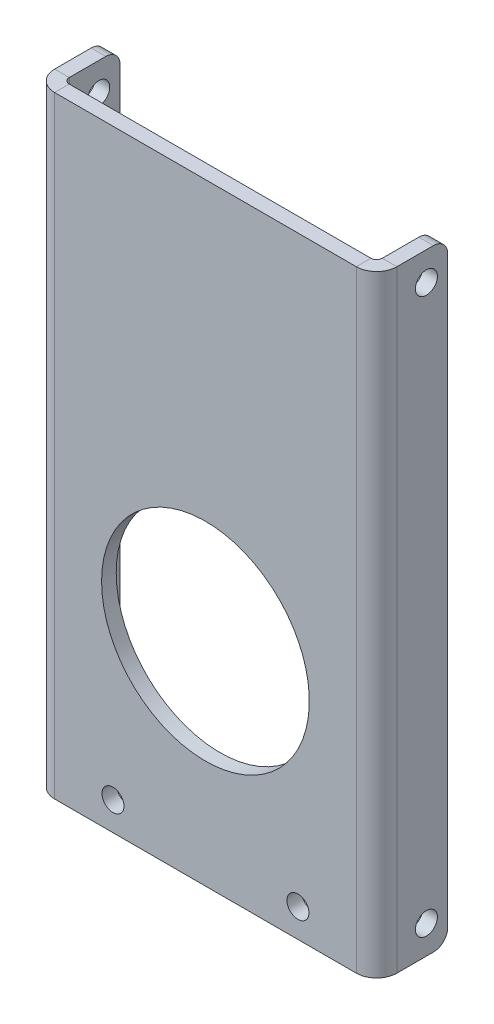
SolidWorks part; units mm, degrees
note: The reader was unsure of these and kept them because the rebuilt part matched: flange length of "Edge-Flange1".
material "5052-H32"
ref_plane "Front Plane" through (0, 0, 0) normal (0, 0, 1) x (1, 0, 0)
ref_plane "Top Plane" through (0, 0, 0) normal (0, 1, 0) x (1, 0, 0)
ref_plane "Right Plane" through (0, 0, 0) normal (1, 0, 0) x (0, 0, -1)
sketch "Sketch1" plane through (0, 0, 0) normal (0, 0, 1) x (1, 0, 0)
  line L0 (-38.1889, 0) -> (38.1889, 0) construction
  line L1 (-38.1889, 89.1964) -> (38.1889, 89.1964)
  line L2 (-38.1889, 89.1964) -> (-38.1889, -47.3286)
  line L3 (-38.1889, -47.3286) -> (38.1889, -47.3286)
  line L4 (38.1889, 89.1964) -> (38.1889, -47.3286)
  point P6 (0, 0)
  dimension "D1" = 47.3286
  dimension "D2" = 76.3778
  dimension "D3" = 136.525
base flange "Base-Flange1" sketch "Sketch1" thickness 3.2639 reverse thickness direction no parameters "D1"=1.27
edge flange "Edge-Flange1" sketch "Sketch27" flange profiles "Sketch27", "Sketch28" flange angle 90 flange length 15.875 flange position material inside bend radius 1.27 thickness 3.2639 relief rectangular parameters "D6"=10, "D8"=0.254
sketch "Sketch27" plane through (38.1889, 0, -3.2639) normal (-1, 0, 0) x (0, 1, 0)
  line L2 (-47.3286, 0) -> (-47.3286, 12.6111)
  line L3 (-47.3286, 12.6111) -> (89.1964, 12.6111)
  line L4 (89.1964, 12.6111) -> (89.1964, 0)
  line L5 (89.1964, 0) -> (-47.3286, 0) construction
  line L6 (89.1964, 0) -> (-47.3286, 0)
sketch "Sketch28" plane through (-38.1889, 0, -3.2639) normal (1, 0, 0) x (0, -1, 0)
  line L0 (47.3286, 0) -> (-89.1964, 0) construction
  line L1 (47.3286, 0) -> (-89.1964, 0)
  line L2 (47.3286, 0) -> (47.3286, 12.6111)
  line L3 (47.3286, 12.6111) -> (-89.1964, 12.6111)
  line L4 (-89.1964, 12.6111) -> (-89.1964, 0)
bend "EdgeBend1" bend radius 1.27 bend angle 90 parameters "D5"=1
bend "EdgeBend2" bend radius 1.27 bend angle 90 parameters "D5"=2
sketch "Sketch29" plane through (38.1889, 0, 0) normal (1, 0, 0) x (0, 0, -1)
  line L0 (11.1125, 82.8464) -> (11.1125, -40.9786) construction
  line L1 (15.875, -47.3286) -> (4.5339, -47.3286) construction
  line L2 (4.5339, 89.1964) -> (15.875, 89.1964) construction
  line L3 (0, -47.3286) -> (0, 89.1964) construction
  dimension "D1" = 6.35
  dimension "D2" = 6.35
  dimension "D3" = 11.1125
hole_wizard "#10 (0.1935) Diameter Hole1" positions "Sketch30" profile "Sketch31" hole size "#10" standard "ANSI Inch" end condition through all
sketch "Sketch30" plane through (38.1889, 0, 0) normal (1, 0, 0) x (0, 0, -1)
  point P0 (11.1125, 82.8464)
  point P3 (11.1125, -40.9786)
sketch "Sketch31" plane through (38.1889, 82.8464, -11.1125) normal (0, 1, 0) x (0, 0, -1)
  line L0 (0, 0) -> (0, 76.3778)
  line L1 (0, 76.3778) -> (2.4574, 76.3778)
  line L2 (2.4574, 76.3778) -> (2.4574, 0)
  line L5 (2.4574, 0) -> (0, 0)
  line L11 (0, -6.35) -> (0, 107.95) construction
  dimension "Thru Hole Dia." = 4.9149
  dimension "Thru Hole Depth" = 76.3778
sketch "Sketch32" plane through (0, 0, -3.2639) normal (0, 0, -1) x (-1, 0, 0)
  circle A0 centre (0, 0) radius 23.1775
  dimension "D1" = 46.355
extrude "Cut-Extrude1" cut sketch "Sketch32" against normal through all normal cut yes
sketch "Sketch33" plane through (0, 0, 0) normal (0, 0, 1) x (1, 0, 0)
  line L0 (-20.6375, -40.9786) -> (20.6375, -40.9786) construction
  line L1 (-38.1889, -47.3286) -> (38.1889, -47.3286) construction
  point P2 (0, -40.9786)
  dimension "D1" = 6.35
  dimension "D2" = 41.275
hole_wizard "#10 (0.1935) Diameter Hole2" positions "Sketch34" profile "Sketch35" hole size "#10" standard "ANSI Inch" end condition up to next
sketch "Sketch34" plane through (0, 0, 0) normal (0, 0, 1) x (1, 0, 0)
  point P0 (-20.6375, -40.9786)
  point P3 (20.6375, -40.9786)
sketch "Sketch35" plane through (-20.6375, -40.9786, 0) normal (1, 0, 0) x (0, -1, 0)
  line L0 (0, 0) -> (0, 3.2639)
  line L1 (0, 3.2639) -> (2.4574, 3.2639)
  line L2 (2.4574, 3.2639) -> (2.4574, 0)
  line L5 (2.4574, 0) -> (0, 0)
  line L11 (0, -6.35) -> (0, 107.95) construction
  dimension "Thru Hole Dia." = 4.9149
  dimension "Thru Hole Depth" = 3.2639
fillet "Fillet1" radius 3.175 4 edges at (-36.557, 89.1964, -15.875) (36.557, 89.1964, -15.875) (-36.557, -47.3286, -15.875) (36.557, -47.3286, -15.875)
sketch "Bend-Lines1" [suppressed] plane through (0, 0, 0) normal (0, 1, 0) x (1, 0, 0)
sketch "Bounding-Box1" [suppressed] plane through (0, 0, 0) normal (0, 1, 0) x (1, 0, 0)
sheet metal parameters "Sheet-Metal1" thickness 3.2639 parameters "D1"=1.27
flat pattern "Flat-Pattern1" [suppressed]
sketch "Bend-Lines2" plane through (0, 0, 0) normal (0, 1, 0) x (1, 0, 0)
sketch3d "Bounding-Box2" [suppressed]
  line L0 (38.1, 56.2696, 0) -> (38.1, -45.3304, 0) construction
  line L1 (-38.1, 56.2696, 0) -> (-38.1, -45.3304, 0) construction
  line L2 (38.1, 56.2696, 0) -> (-38.1, 56.2696, 0) construction
  line L3 (38.1, -45.3304, 0) -> (-38.1, -45.3304, 0) construction
sheet metal parameters "Sheet-Metal8" thickness 3.2639 parameters "D1"=1.27
flat pattern "Flat-Pattern1"
sketch "Bend-Lines2" plane through (0, 0, 0) normal (0, 0, 1) x (1, 0, 0)
  line L0 (-35.8453, 56.2696) -> (-35.8453, -45.3304) construction
  line L1 (35.8453, -45.3304) -> (35.8453, 56.2696) construction
  line L2 (-35.8453, 56.2696) -> (-35.8453, -45.3304) construction
  line L3 (35.8453, -45.3304) -> (35.8453, 56.2696) construction
sketch3d "Bounding-Box2" [suppressed]
  line L0 (49.4656, 56.2696, 0) -> (49.4656, -45.3304, 0) construction
  line L1 (-49.4656, 56.2696, 0) -> (-49.4656, -45.3304, 0) construction
  line L2 (49.4656, 56.2696, 0) -> (-49.4656, 56.2696, 0) construction
  line L3 (49.4656, -45.3304, 0) -> (-49.4656, -45.3304, 0) construction
bend of the flat pattern "Flatten-<EdgeBend1>1"
bend of the flat pattern "Flatten-<EdgeBend2>1"
sheet metal parameters "Sheet-Metal9" thickness 3.2639 parameters "D1"=1.27
flat pattern "Flat-Pattern1" [suppressed]
sketch "Bend-Lines2" plane through (0, 0, 0) normal (0, 0, 1) x (1, 0, 0)
  line L0 (-35.8453, 56.2696) -> (-35.8453, -45.3304) construction
  line L1 (35.8453, -45.3304) -> (35.8453, 56.2696) construction
  line L2 (-35.8453, 56.2696) -> (-35.8453, -45.3304) construction
  line L3 (35.8453, -45.3304) -> (35.8453, 56.2696) construction
sketch3d "Bounding-Box2" [suppressed]
  line L0 (49.4656, 56.2696, 0) -> (49.4656, -45.3304, 0) construction
  line L1 (-49.4656, 56.2696, 0) -> (-49.4656, -45.3304, 0) construction
  line L2 (49.4656, 56.2696, 0) -> (-49.4656, 56.2696, 0) construction
  line L3 (49.4656, -45.3304, 0) -> (-49.4656, -45.3304, 0) construction
bend of the flat pattern "Flatten-<EdgeBend1>1"
bend of the flat pattern "Flatten-<EdgeBend2>1"
sketch "Sketch29-1" [suppressed] plane through (33.5906, 0, 0) normal (0, 0, 1) x (1, 0, 0)
  line L0 (11.1125, 49.9196) -> (11.1125, -38.9804) construction
  line L1 (15.875, -45.3304) -> (-83.0561, -45.3304)
  line L2 (-83.0561, 56.2696) -> (15.875, 56.2696)
  line L3 (0, -45.3304) -> (0, 56.2696)
  dimension "D1" = 6.35
  dimension "D2" = 6.35
  dimension "D3" = 11.1125
sheet metal parameters "Sheet-Metal10" thickness 3.2639 parameters "D1"=1.27
flat pattern "Flat-Pattern1" [suppressed]
sketch "Bend-Lines2" plane through (0, 0, 0) normal (0, 0, 1) x (1, 0, 0)
  line L0 (-35.8453, 82.8464) -> (-35.8453, -47.3286) construction
  line L1 (35.8453, -47.3286) -> (35.8453, 82.8464) construction
  line L2 (-35.8453, 82.8464) -> (-35.8453, -47.3286) construction
  line L3 (35.8453, -47.3286) -> (35.8453, 82.8464) construction
sketch3d "Bounding-Box2" [suppressed]
  line L0 (49.4656, 82.8464, 0) -> (49.4656, -47.3286, 0) construction
  line L1 (-49.4656, 82.8464, 0) -> (-49.4656, -47.3286, 0) construction
  line L2 (49.4656, 82.8464, 0) -> (-49.4656, 82.8464, 0) construction
  line L3 (49.4656, -47.3286, 0) -> (-49.4656, -47.3286, 0) construction
bend of the flat pattern "Flatten-<EdgeBend1>1"
bend of the flat pattern "Flatten-<EdgeBend2>1"
sketch "Sketch29-1" [suppressed] plane through (33.5906, 0, 0) normal (0, 0, 1) x (1, 0, 0)
  line L0 (11.1125, 76.4964) -> (11.1125, -40.9786) construction
  line L1 (15.875, -47.3286) -> (-83.0561, -47.3286)
  line L2 (-83.0561, 82.8464) -> (15.875, 82.8464)
  line L3 (0, -47.3286) -> (0, 82.8464)
  dimension "D1" = 6.35
  dimension "D2" = 6.35
  dimension "D3" = 11.1125
sheet metal parameters "Sheet-Metal11" thickness 3.2639 parameters "D1"=1.27
flat pattern "Flat-Pattern1" [suppressed]
sketch "Bend-Lines2" plane through (0, 0, 0) normal (0, 0, 1) x (1, 0, 0)
  line L0 (-35.9342, 89.1964) -> (-35.9342, -47.3286) construction
  line L1 (35.9342, -47.3286) -> (35.9342, 89.1964) construction
  line L2 (-35.9342, 89.1964) -> (-35.9342, -47.3286) construction
  line L3 (35.9342, -47.3286) -> (35.9342, 89.1964) construction
sketch3d "Bounding-Box2" [suppressed]
  line L0 (49.5543, -47.3286, 0) -> (49.5545, 89.1964, 0) construction
  line L1 (-49.5545, -47.3285, 0) -> (-49.5543, 89.1965, 0) construction
  line L2 (49.5543, -47.3286, 0) -> (-49.5545, -47.3285, 0) construction
  line L3 (49.5545, 89.1964, 0) -> (-49.5543, 89.1965, 0) construction
bend of the flat pattern "Flatten-<EdgeBend1>1"
bend of the flat pattern "Flatten-<EdgeBend2>1"
sketch "Sketch29-1" [suppressed] plane through (33.6795, 0, 0) normal (0, 0, 1) x (1, 0, 0)
  line L0 (11.1125, 82.8464) -> (11.1125, -40.9786) construction
  line L1 (12.7, -47.3286) -> (-80.0589, -47.3286)
  line L2 (-80.0589, 89.1964) -> (12.7, 89.1964)
  line L3 (0, -47.3286) -> (0, 89.1964)
  dimension "D1" = 6.35
  dimension "D2" = 6.35
  dimension "D3" = 11.1125
